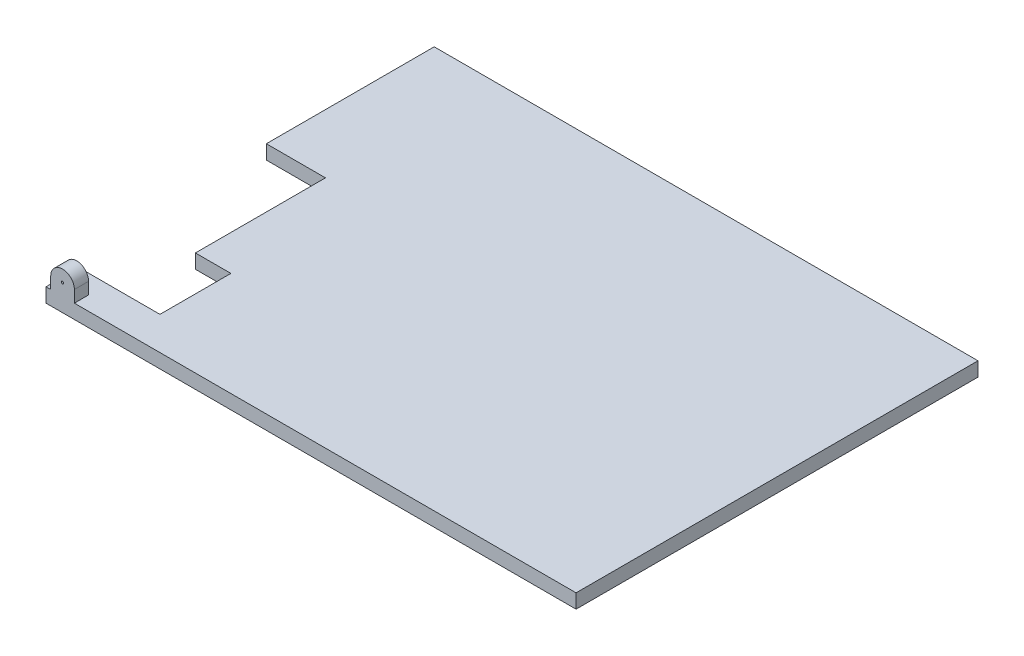
SolidWorks part; units mm, degrees
material "Acrilico TEC"
ref_plane "Front Plane" through (0, 0, 0) normal (0, 0, 1) x (1, 0, 0)
ref_plane "Top Plane" through (0, 0, 0) normal (0, 1, 0) x (1, 0, 0)
ref_plane "Right Plane" through (0, 0, 0) normal (1, 0, 0) x (0, 0, -1)
sketch "Sketch1" plane through (0, 0, 0) normal (0, 1, 0) x (1, 0, 0)
  line L1 (5.8044, 4.7967) -> (230, 4.7967)
  line L2 (0, 103.7967) -> (0, 174.7967)
  line L3 (0, 174.7967) -> (230, 174.7967)
  line L4 (230, 4.7967) -> (230, 174.7967)
  line L7 (18.8044, 18.7967) -> (25, 18.7967)
  line L8 (25, 48.7967) -> (25, 103.7967)
  line L9 (25, 103.7967) -> (0, 103.7967)
  line L10 (25, 18.7967) -> (40, 18.7967)
  line L11 (40, 18.7967) -> (40, 48.7967)
  line L12 (40, 48.7967) -> (25, 48.7967)
  line L13 (5.8044, 4.7967) -> (5.8044, 18.7967)
  line L14 (5.8044, 18.7967) -> (18.8044, 18.7967)
  dimension "D2" = 170
  dimension "D3" = 230
  dimension "D4" = 13
  dimension "D5" = 25
  dimension "D6" = 85
  dimension "D7" = 14
  dimension "D8" = 15
  dimension "D9" = 30
  dimension "D10" = 15
  dimension "D11" = 6.1956
extrude "Boss-Extrude1" add sketch "Sketch1" along normal blind 6
sketch "Sketch2" plane through (0, 0, -4.7967) normal (0, 0, 1) x (1, 0, 0)
  line L0 (5.8044, 6) -> (230, 6) construction
  line L1 (5.8044, 6) -> (5.8044, 0) construction
  line L2 (7.8044, 6) -> (17.8044, 6)
  line L3 (7.8044, 6) -> (7.8044, 11)
  line L5 (17.8044, 6) -> (17.8044, 11)
  arc A0 (17.8044, 11) -> (7.8044, 11) centre (12.8044, 11) ccw
  circle A1 centre (12.8044, 11) radius 0.5
  dimension "D3" = 1
  dimension "D4" = 5
  dimension "D1" = 5
  dimension "D2" = 10
  dimension "D5" = 2
extrude "Boss-Extrude2" add sketch "Sketch2" against normal blind 6
